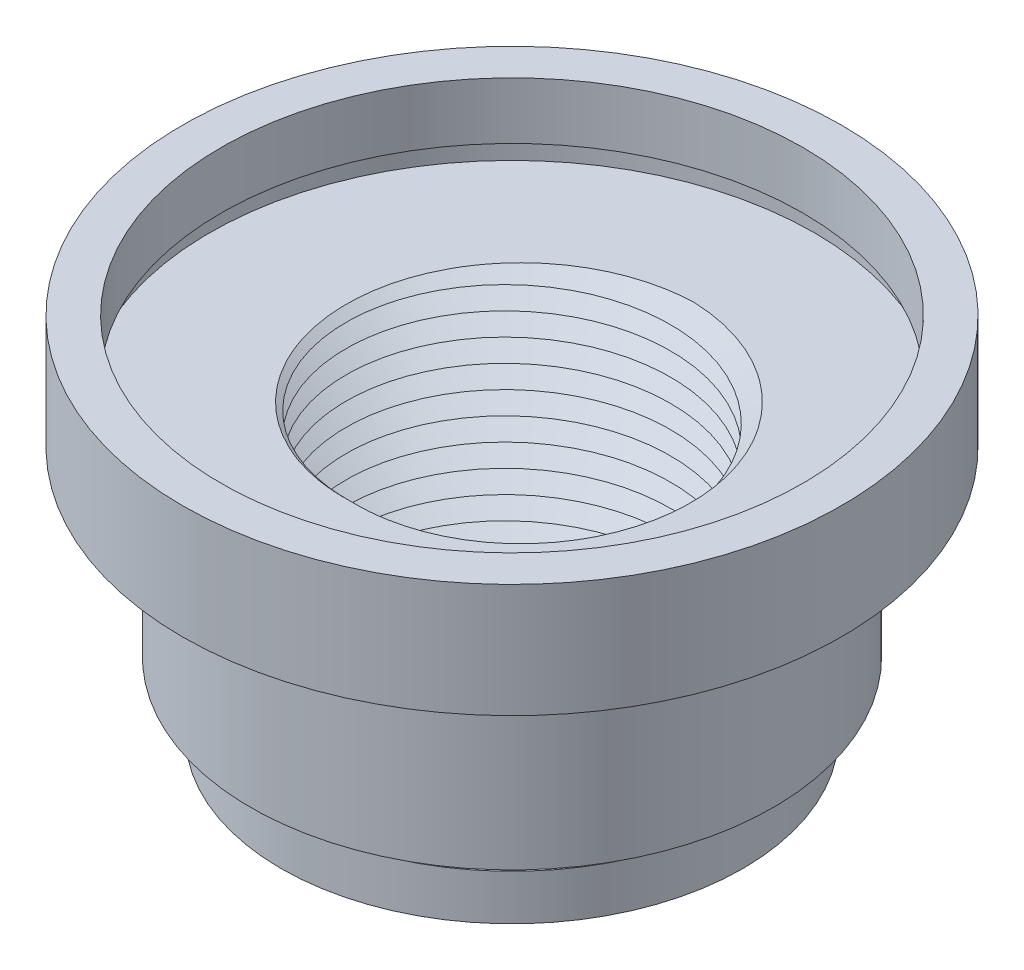
SolidWorks part; units mm, degrees
ref_plane "Ebene vorne" through (0, 0, 0) normal (0, 0, 1) x (1, 0, 0)
ref_plane "Ebene oben" through (0, 0, 0) normal (0, 1, 0) x (1, 0, 0)
ref_plane "Ebene rechts" through (0, 0, 0) normal (1, 0, 0) x (0, 0, -1)
sketch "Skizze1" plane through (0, 0, 0) normal (0, 0, 1) x (1, 0, 0)
  line L0 (0, -44.362) -> (0, 55.352) construction
  line L1 (-10.16, 0) -> (-7, 0)
  line L2 (-11.5, 3) -> (-11.5, 11)
  line L3 (-11.5, 11) -> (-14.5, 11)
  line L5 (-7, 12.5) -> (-13.3, 12.5)
  line L6 (-12.8, 13.5) -> (-12.8, 16)
  line L7 (-12.8, 16) -> (-14.5, 16)
  line L8 (-14.5, 16) -> (-14.5, 11)
  line L9 (-11.5, 3) -> (-9.66, 3)
  line L10 (-10.16, 0) -> (-10.16, 2)
  line L11 (-10.16, 2) -> (-9.66, 2)
  line L12 (-9.66, 2) -> (-9.66, 3)
  line L13 (-13.3, 12.5) -> (-13.3, 13.5)
  line L14 (-13.3, 13.5) -> (-12.8, 13.5)
  line L15 (-7, 0) -> (-7, 12.5)
  dimension "D2" = 14
  dimension "D3" = 20.32
  dimension "D4" = 25.6
  dimension "D5" = 3
  dimension "D6" = 1
  dimension "D7" = 0.5
  dimension "D8" = 0.5
  dimension "D9" = 1
  dimension "D10" = 8
  dimension "D11" = 23
  dimension "D12" = 1.5
  dimension "D13" = 29
  dimension "D14" = 5
  dimension "D15" = 16
  dimension "D16" = 1.2
revolve "Rotation1" add sketch "Skizze1" angle 360 about L0
cosmetic thread "Gewindedarstellung1" parameters "D1"=2, "D2"=19.6
cosmetic thread "Gewindedarstellung2" parameters "D1"=3, "D2"=26.289
cosmetic thread "Gewindedarstellung3" [suppressed] parameters "D2"=16
sketch "Skizze6" plane through (0, 0, 0) normal (0, 1, 0) x (1, 0, 0)
  circle A0 centre (0, 0) radius 7.5
  dimension "D1" = 15
curve "Spirale/Helix1" pitch 1 height 14 turns 14
sketch "Skizze7" plane through (0, 0, 0) normal (1, 0, 0) x (0, 0, -1)
  line L0 (-8.4995, -1) -> (0, -1) construction
  line L1 (-7, -0.4226) -> (-8, -1)
  line L2 (-8, -1) -> (-7, -1.5774)
  line L3 (-7, -1.5774) -> (-7, -0.4226)
  dimension "D1" = 60
  dimension "D2" = 8
  dimension "D3" = 1
  dimension "D4" = 1
sweep "Schnitt-Austragung1" cut profiles "Skizze7" path "Spirale/Helix1"
